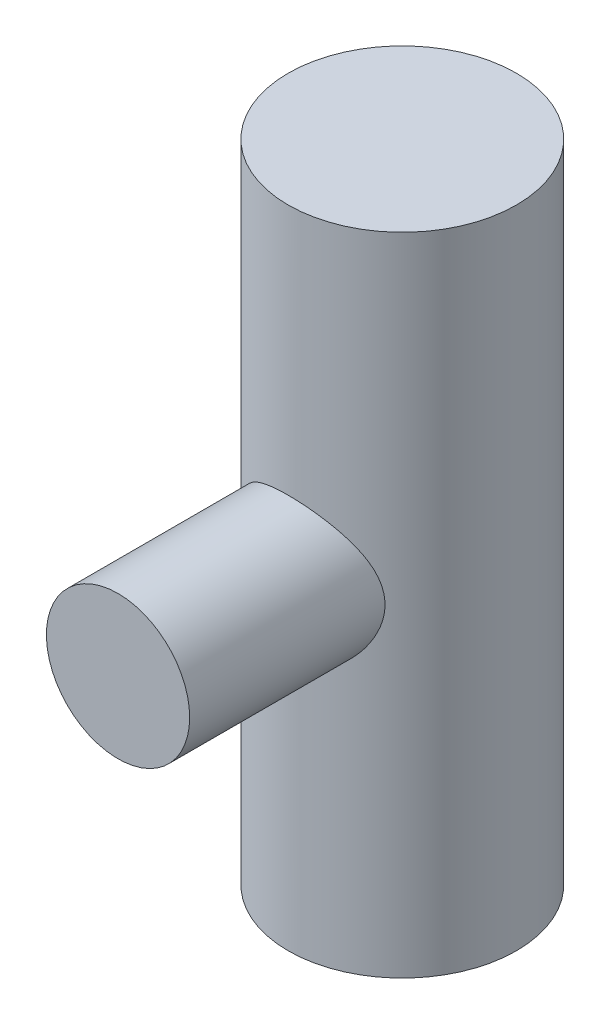
SolidWorks part; units mm, degrees
material "Brass"
ref_plane "Front Plane" through (0, 0, 0) normal (0, 0, 1) x (1, 0, 0)
ref_plane "Top Plane" through (0, 0, 0) normal (0, 1, 0) x (1, 0, 0)
ref_plane "Right Plane" through (0, 0, 0) normal (1, 0, 0) x (0, 0, -1)
sketch "Sketch1" plane through (0, 0, 0) normal (0, 1, 0) x (1, 0, 0)
  circle A0 centre (0, 0) radius 12.75
  dimension "D1" = 25.5
extrude "Boss-Extrude1" add sketch "Sketch1" along normal blind 36.068 and the other way blind 36.068
sketch "Sketch2" plane through (0, 0, 0) normal (0, 0, 1) x (1, 0, 0)
  circle A0 centre (0, 0) radius 8
  dimension "D1" = 16
extrude "Boss-Extrude2" add sketch "Sketch2" along normal blind 31.75
